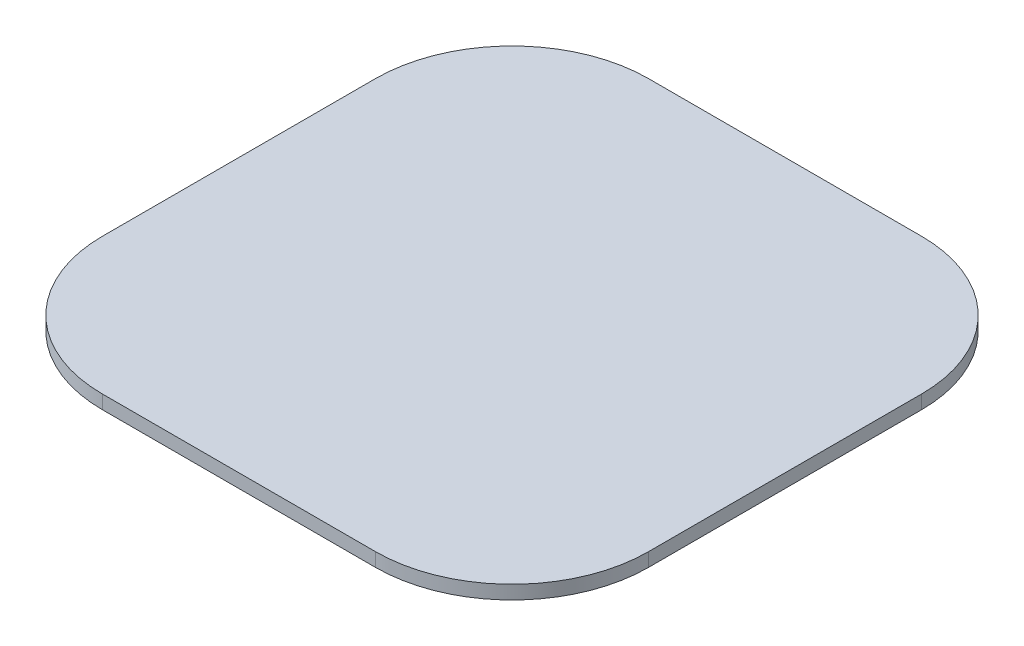
SolidWorks part; units mm, degrees
material "Acrylic (Medium-high impact)"
ref_plane "Front Plane" through (0, 0, 0) normal (0, 0, 1) x (1, 0, 0)
ref_plane "Top Plane" through (0, 0, 0) normal (0, 1, 0) x (1, 0, 0)
ref_plane "Right Plane" through (0, 0, 0) normal (1, 0, 0) x (0, 0, -1)
sketch "Sketch1" plane through (0, 0, 0) normal (0, 1, 0) x (1, 0, 0)
  line L1 (-127, -127) -> (127, -127)
  line L2 (-127, -127) -> (-127, 127)
  line L3 (-127, 127) -> (127, 127)
  line L4 (127, -127) -> (127, 127)
  line L5 (-127, -127) -> (127, 127) construction
  line L6 (-127, 127) -> (127, -127) construction
  point P0 (0, 0)
  dimension "D1" = 254
  dimension "D2" = 254
extrude "Boss-Extrude1" add sketch "Sketch1" along normal blind 6.35
sketch "Sketch2" plane through (0, 6.35, 0) normal (0, 1, 0) x (1, 0, 0)
  line L0 (-127, -127) -> (-127, -63.5)
  line L1 (-127, 127) -> (-127, -127) construction
  line L2 (-127, -127) -> (-63.5, -127)
  line L3 (-127, -127) -> (127, -127) construction
  line L5 (0, -3.4925) -> (0, 3.4925) construction
  line L6 (-3.4925, 0) -> (3.4925, 0) construction
  line L7 (63.5, -127) -> (127, -127)
  line L8 (127, -127) -> (127, -63.5)
  line L9 (127, 63.5) -> (127, 127)
  line L10 (127, 127) -> (63.5, 127)
  line L11 (-63.5, 127) -> (-127, 127)
  line L12 (-127, 127) -> (-127, 63.5)
  arc A0 (-127, -63.5) -> (-63.5, -127) centre (-63.5, -63.5) ccw
  arc A1 (127, -63.5) -> (63.5, -127) centre (63.5, -63.5) cw
  arc A2 (127, 63.5) -> (63.5, 127) centre (63.5, 63.5) ccw
  arc A3 (-127, 63.5) -> (-63.5, 127) centre (-63.5, 63.5) cw
extrude "Cut-Extrude1" cut sketch "Sketch2" against normal through all
